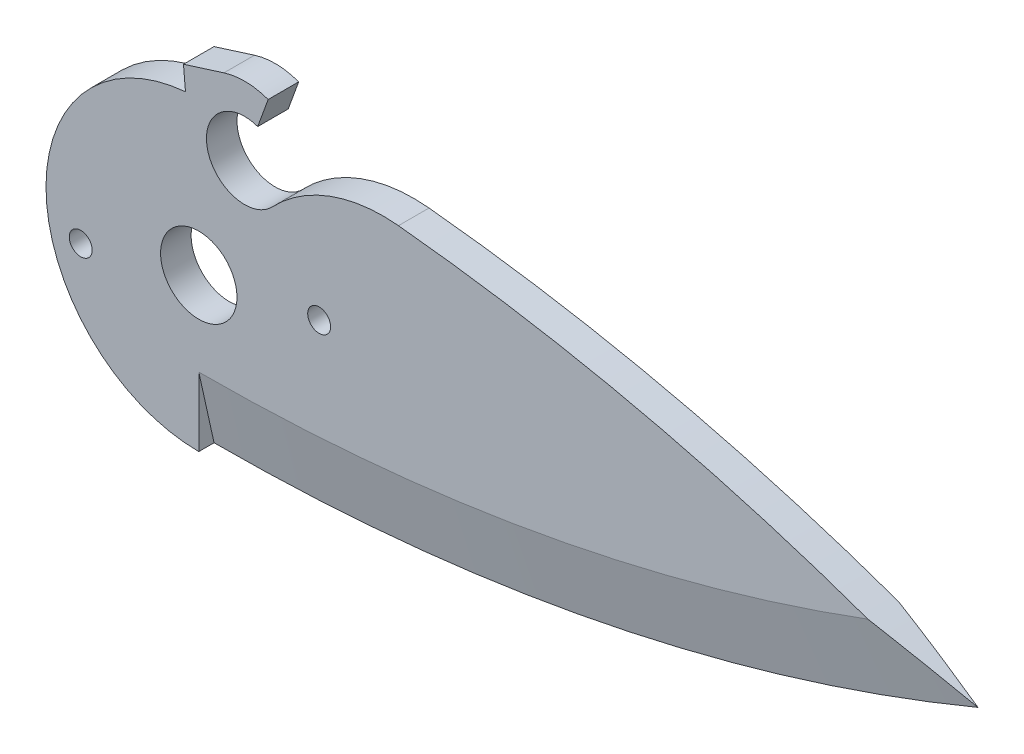
SolidWorks part; units mm, degrees
material "Obyčejná uhlíková ocel"
ref_plane "Přední rovina" through (0, 0, 0) normal (0, 0, 1) x (1, 0, 0)
ref_plane "Horní rovina" through (0, 0, 0) normal (0, 1, 0) x (1, 0, 0)
ref_plane "Pravá rovina" through (0, 0, 0) normal (1, 0, 0) x (0, 0, -1)
sketch "Skica1" plane through (0, 0, 0) normal (0, 0, 1) x (1, 0, 0)
  line L0 (0, 0) -> (28.9614, 0) construction
  line L1 (1.6465, 12.2916) -> (-1.0023, 11.4562)
  line L2 (-1.0023, 11.4562) -> (-0.8716, 9.9619)
  line L3 (0, 10) -> (0, -10) construction
  line L4 (3, 8) -> (3, 16.5233) construction
  line L5 (3.8551, 10.3492) -> (4.5391, 12.2286)
  line L7 (0, 0) -> (58.3677, 0) construction
  line L8 (0, 0) -> (-0.0542, 0.0512) construction
  circle A0 centre (0, 0) radius 2.5
  arc A1 (-0.8716, 9.9619) -> (-10, 0) centre (0, 0) ccw
  arc A2 (13.0692, 9.3414) -> (50, 0) centre (0, -120) cw
  arc A3 (0, -10) -> (50, 0) centre (0, 120) ccw
  arc A4 (3.8551, 10.3492) -> (4.8128, 6.2784) centre (3, 8) ccw
  arc A5 (13.0692, 9.3414) -> (4.8128, 6.2784) centre (12.0638, -0.6079) ccw
  arc A6 (4.5391, 12.2286) -> (1.6465, 12.2916) centre (3, 8) ccw
  arc A9 (-10, 0) -> (0, -10) centre (0, 0) ccw
  dimension "D1" = 10
  dimension "D2" = 5
  dimension "D3" = 60
  dimension "D5" = 2.5
  dimension "D6" = 2
  dimension "D8" = 10
  dimension "D11" = 5
  dimension "D12" = 0
  dimension "D4" = 3
  dimension "D7" = 20
  dimension "D9" = 1.5
  dimension "D10" = 8
extrude "Přidat vysunutím1" add sketch "Skica1" along normal mid plane 2
sketch "Skica4" plane through (0, 0, 0) normal (0, 0, 1) x (1, 0, 0)
  line L0 (0, 0) -> (7.8785, 1.3892) construction
  line L1 (0, 0) -> (27.9086, 0) construction
  line L2 (0, 0) -> (-7.7274, -2.0706) construction
  line L3 (-1.0023, 11.4562) -> (-0.8716, 9.9619) construction
  circle A0 centre (7.8785, 1.3892) radius 0.75
  circle A1 centre (-7.7274, -2.0706) radius 0.75
  dimension "D2" = 1.5
  dimension "D1" = 8
  dimension "D3" = 10
  dimension "D4" = 100
extrude "Odebrat vysunutím1" cut sketch "Skica4" against normal through all and the other way through all
sketch "Skica2" plane through (0, 0, 0) normal (1, 0, 0) x (0, 0, -1)
  line L0 (0, -10) -> (1, -5.4893)
  line L1 (-1, -10) -> (1, -10) construction
  line L2 (1, -10) -> (1, 9.9619) construction
  line L3 (0, -10) -> (0, -2.6677) construction
  line L4 (0, -10) -> (-1, -5.4893)
  line L5 (-1, -5.4893) -> (-1, -10)
  line L6 (-1, -10) -> (0, -10)
  line L7 (1, -5.4893) -> (1, -10)
  line L8 (1, -10) -> (0, -10)
  line L9 (0, -10) -> (0.0115, -9.9693)
  dimension "D1" = 25
sketch "Skica3" plane through (0, 0, 0) normal (0, 0, 1) x (1, 0, 0)
  arc A0 (0, -10) -> (50, 0) centre (0, 120) ccw construction
  arc A1 (0, -10) -> (50, 0) centre (0, 120) ccw
sweep "Odebrat tažením po křivce1" cut profiles "Skica2" path "Skica3"
mirror "Zrcadlit1" about plane through (0, 0, 0) normal (0, 0, 1) of "Odebrat tažením po křivce1"
sketch "Skica5" plane through (0, 0, -1) normal (0, 0, -1) x (-1, 0, 0)
  circle A0 centre (-13.6099, 7.7362) radius 0.9715
extrude "Přidat vysunutím2" [suppressed] add sketch "Skica5" along normal blind 2
